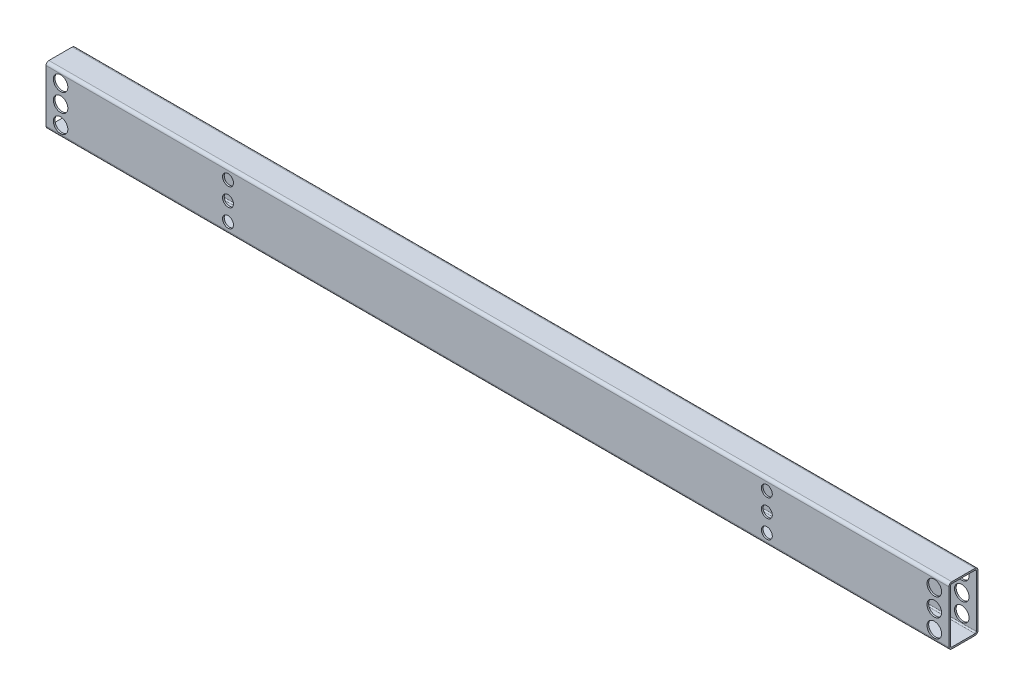
SolidWorks part; units mm, degrees
material "6061-T6 (SS)"
ref_plane "Front" through (0, 0, 0) normal (0, 0, 1) x (1, 0, 0)
ref_plane "Top" through (0, 0, 0) normal (0, 1, 0) x (1, 0, 0)
ref_plane "Right" through (0, 0, 0) normal (1, 0, 0) x (0, 0, -1)
sketch "Sketch1" plane through (0, 0, 0) normal (1, 0, 0) x (0, 0, -1)
  line L0 (10.16, -25.4) -> (-10.16, -25.4)
  line L1 (12.7, -22.86) -> (12.7, 22.86)
  line L2 (10.16, 25.4) -> (-10.16, 25.4)
  line L3 (-12.7, -22.86) -> (-12.7, 22.86)
  line L4 (12.7, -25.4) -> (-12.7, 25.4) construction
  line L5 (12.7, 25.4) -> (-12.7, -25.4) construction
  arc A0 (-10.16, -25.4) -> (-12.7, -22.86) centre (-10.16, -22.86) cw
  arc A1 (10.16, -25.4) -> (12.7, -22.86) centre (10.16, -22.86) ccw
  arc A2 (12.7, 22.86) -> (10.16, 25.4) centre (10.16, 22.86) ccw
  arc A3 (-10.16, 25.4) -> (-12.7, 22.86) centre (-10.16, 22.86) ccw
  point P0 (0, 0)
  dimension "D3" = 2.54
  dimension "D1" = 25.4
  dimension "D2" = 50.8
extrude "Extrude-Thin1" add sketch "Sketch1" along normal mid plane 787.4 thin thin type one direction reverse wall 1.4478
hole_wizard "1/2 (0.5) Diameter Hole1" positions "Sketch2" profile "Sketch3" hole size "1/2" standard "ANSI Inch" end condition through all
sketch "Sketch2" plane through (0, 0, -12.7) normal (0, 0, -1) x (-1, 0, 0)
  line L0 (-393.7, -22.86) -> (-393.7, 22.86) construction
  line L1 (-393.7, 25.4) -> (393.7, 25.4) construction
  line L2 (-393.7, -25.4) -> (393.7, -25.4) construction
  line L3 (-381, 15.875) -> (-381, -15.875) construction
  line L4 (0, 0) -> (0, -37.3791) construction
  point P0 (-381, 15.875)
  point P2 (-381, -15.875)
  point P15 (-381, 0)
  point P23 (381, -15.875)
  point P24 (381, 0)
  point P25 (381, 15.875)
  dimension "D1" = 12.7
  dimension "D2" = 9.525
  dimension "D3" = 9.525
sketch "Sketch3" plane through (381, 15.875, -12.7) normal (1, 0, 0) x (0, 1, 0)
  line L0 (0, 0) -> (0, 25.4)
  line L1 (0, 25.4) -> (6.35, 25.4)
  line L2 (6.35, 25.4) -> (6.35, 0)
  line L5 (6.35, 0) -> (0, 0)
  line L11 (0, -6.35) -> (0, 107.95) construction
  dimension "Thru Hole Dia." = 12.7
  dimension "Thru Hole Depth" = 25.4
hole_wizard "3/8 (0.375) Diameter Hole1" positions "Sketch4" profile "Sketch5" hole size "3/8" standard "ANSI Inch" end condition through all
sketch "Sketch4" plane through (0, 0, -12.7) normal (0, 0, -1) x (-1, 0, 0)
  line L0 (-234.95, 15.875) -> (-234.95, -15.875) construction
  line L2 (-393.7, 25.4) -> (393.7, 25.4) construction
  line L3 (-393.7, -25.4) -> (393.7, -25.4) construction
  line L4 (0, 0) -> (0, -51.4899) construction
  point P19 (-234.95, 15.875)
  point P21 (-234.95, 0)
  point P23 (-234.95, -15.875)
  point P42 (234.95, -15.875)
  point P43 (234.95, 0)
  point P44 (234.95, 15.875)
  dimension "D1" = 9.525
  dimension "D2" = 9.525
  dimension "D3" = 469.9
sketch "Sketch5" plane through (234.95, 15.875, -12.7) normal (1, 0, 0) x (0, 1, 0)
  line L0 (0, 0) -> (0, 25.4)
  line L1 (0, 25.4) -> (4.7625, 25.4)
  line L2 (4.7625, 25.4) -> (4.7625, 0)
  line L5 (4.7625, 0) -> (0, 0)
  line L11 (0, -6.35) -> (0, 107.95) construction
  dimension "Thru Hole Dia." = 9.525
  dimension "Thru Hole Depth" = 25.4
sketch "Sketch6" plane through (0, 0, -12.7) normal (0, 0, -1) x (-1, 0, 0)
  line L0 (-393.7, -25.4) -> (393.7, -25.4) construction
  line L2 (-120.65, -25.4) -> (-107.95, -25.4)
  line L3 (-120.65, -25.4) -> (-120.65, 15.875)
  line L4 (-117.475, 19.05) -> (-111.125, 19.05)
  line L5 (-107.95, -25.4) -> (-107.95, 15.875)
  line L6 (-44.45, -25.4) -> (-31.75, -25.4)
  line L11 (-44.45, -25.4) -> (-44.45, 15.875)
  line L12 (-41.275, 19.05) -> (-34.925, 19.05)
  line L13 (-31.75, -25.4) -> (-31.75, 15.875)
  line L14 (31.75, -25.4) -> (44.45, -25.4)
  line L15 (31.75, -25.4) -> (31.75, 15.875)
  line L16 (34.925, 19.05) -> (41.275, 19.05)
  line L17 (44.45, -25.4) -> (44.45, 15.875)
  line L18 (107.95, -25.4) -> (120.65, -25.4)
  line L19 (107.95, -25.4) -> (107.95, 15.875)
  line L20 (111.125, 19.05) -> (117.475, 19.05)
  line L21 (120.65, -25.4) -> (120.65, 15.875)
  line L22 (0, 0) -> (0, -9.525) construction
  arc A0 (-111.125, 19.05) -> (-107.95, 15.875) centre (-111.125, 15.875) cw
  arc A1 (-120.65, 15.875) -> (-117.475, 19.05) centre (-117.475, 15.875) cw
  arc A4 (-34.925, 19.05) -> (-31.75, 15.875) centre (-34.925, 15.875) cw
  arc A5 (-44.45, 15.875) -> (-41.275, 19.05) centre (-41.275, 15.875) cw
  arc A6 (41.275, 19.05) -> (44.45, 15.875) centre (41.275, 15.875) cw
  arc A7 (31.75, 15.875) -> (34.925, 19.05) centre (34.925, 15.875) cw
  arc A8 (117.475, 19.05) -> (120.65, 15.875) centre (117.475, 15.875) cw
  arc A9 (107.95, 15.875) -> (111.125, 19.05) centre (111.125, 15.875) cw
  dimension "D1" = 3.175
  dimension "D2" = 12.7
  dimension "D3" = 44.45
  dimension "D5" = 76.2
  dimension "D4" = 4
extrude "Cut-Extrude1" cut sketch "Sketch6" against normal blind 9.525
